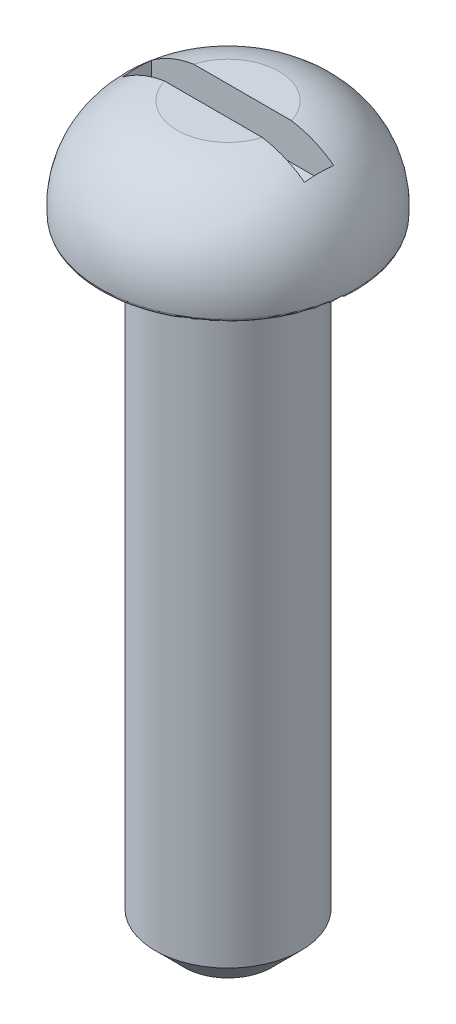
SolidWorks part; units mm, degrees
ref_plane "Спереди" through (0, 0, 0) normal (0, 0, 1) x (1, 0, 0)
ref_plane "Сверху" through (0, 0, 0) normal (0, 1, 0) x (1, 0, 0)
ref_plane "Справа" through (0, 0, 0) normal (1, 0, 0) x (0, 0, -1)
sketch "Эскиз1" plane through (0, 0, 0) normal (0, 0, 1) x (1, 0, 0)
  line L0 (3.5, 17.2) -> (2, 17.2)
  line L1 (0, 0) -> (0, 20)
  line L2 (2, 17.2) -> (2, 0.8)
  line L3 (2, 0.8) -> (1.2, 0)
  line L4 (1.2, 0) -> (0, 0)
  line L5 (0, 20) -> (1.4, 20)
  arc A0 (1.4, 20) -> (3.5, 17.2) centre (1, 17.5125) cw
  dimension "D2" = 1.4
  dimension "D8" = 1
  dimension "D1" = 20
  dimension "D3" = 2
  dimension "D4" = 1.2
  dimension "D5" = 2.8
  dimension "D6" = 3.5
  dimension "D7" = 45
revolve "Повернуть1" add sketch "Эскиз1" angle 360 about L1
fillet "Скругление1" radius 0.1 1 edges at (0, 17.2, -3.5)
sketch "Эскиз3" plane through (0, 20, 0) normal (0, 1, 0) x (-1, 0, 0)
  line L1 (2.5, -0.4) -> (-2.5, -0.4)
  line L2 (2.5, -0.4) -> (2.5, 0.4)
  line L3 (2.5, 0.4) -> (-2.5, 0.4)
  line L4 (-2.5, -0.4) -> (-2.5, 0.4)
  dimension "D1" = 0.8
  dimension "D2" = 0.4
  dimension "D3" = 5
  dimension "D4" = 2.5
extrude "Вырез-Вытянуть2" cut sketch "Эскиз3" against normal blind 1
ref_axis "Ось1" through (0, -9.8623, 0) along (0, 1, 0)
